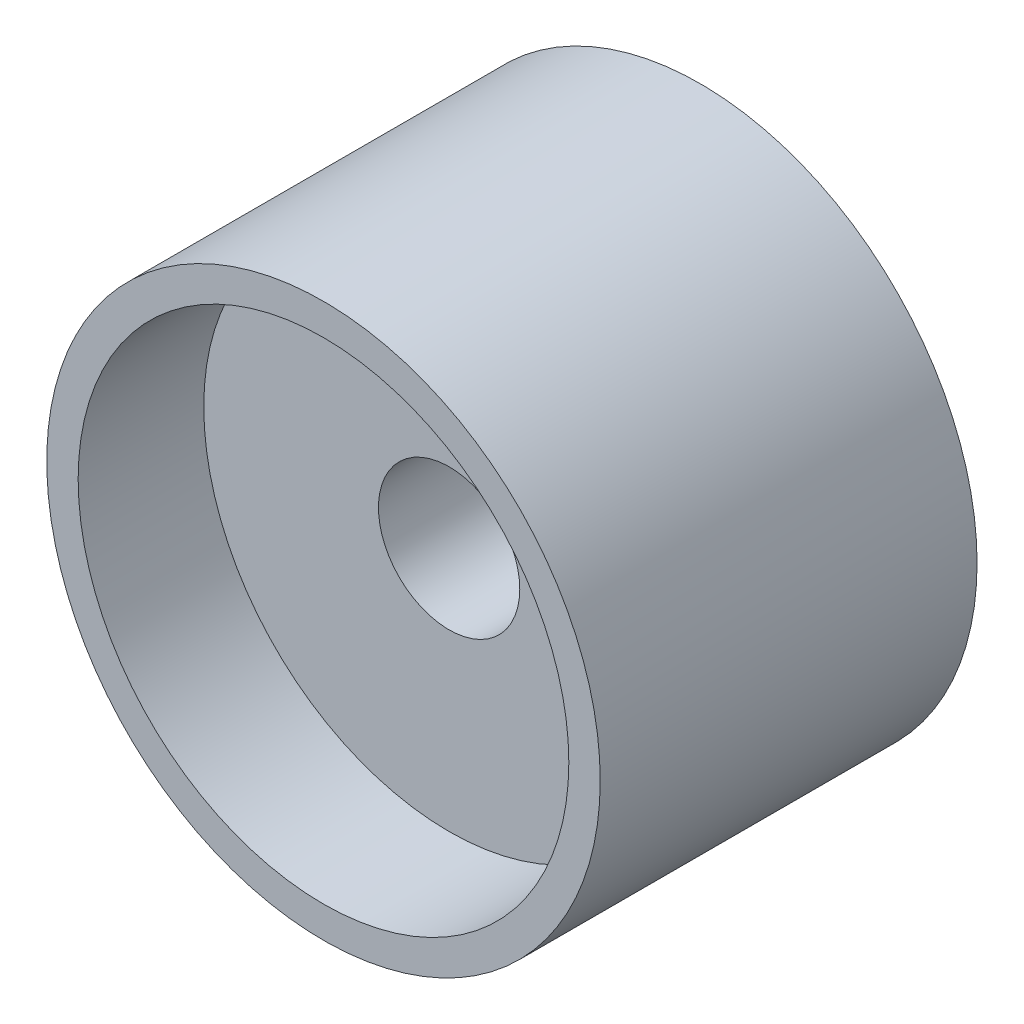
SolidWorks part; units mm, degrees
ref_plane "Front Plane" through (0, 0, 0) normal (0, 0, 1) x (1, 0, 0)
ref_plane "Top Plane" through (0, 0, 0) normal (0, 1, 0) x (1, 0, 0)
ref_plane "Right Plane" through (0, 0, 0) normal (1, 0, 0) x (0, 0, -1)
sketch "Sketch1" plane through (0, 0, 0) normal (0, 0, 1) x (1, 0, 0)
  circle A0 centre (0, 0) radius 4.4062
  circle A1 centre (0, 0) radius 3.9062
  circle A2 centre (0, 0) radius 1.125
  dimension "D1" = 2.25
  dimension "D2" = 7.8125
  dimension "D3" = 0.5
extrude "Boss-Extrude1" add sketch "Sketch1" along normal blind 3 contours A0 A1 region at (-4.2816, 0, 0)
extrude "Boss-Extrude2" add sketch "Sketch1<3>" against normal blind 3 and the other way blind 1 contours A1 A2 | A0 A1 region at (-4.2816, 0, 0) region at (-3.7958, 0, 0)
sketch "Sketch1<3>" plane through (0, 0, 0) normal (0, 0, 1) x (1, 0, 0) same geometry as "Sketch1"
